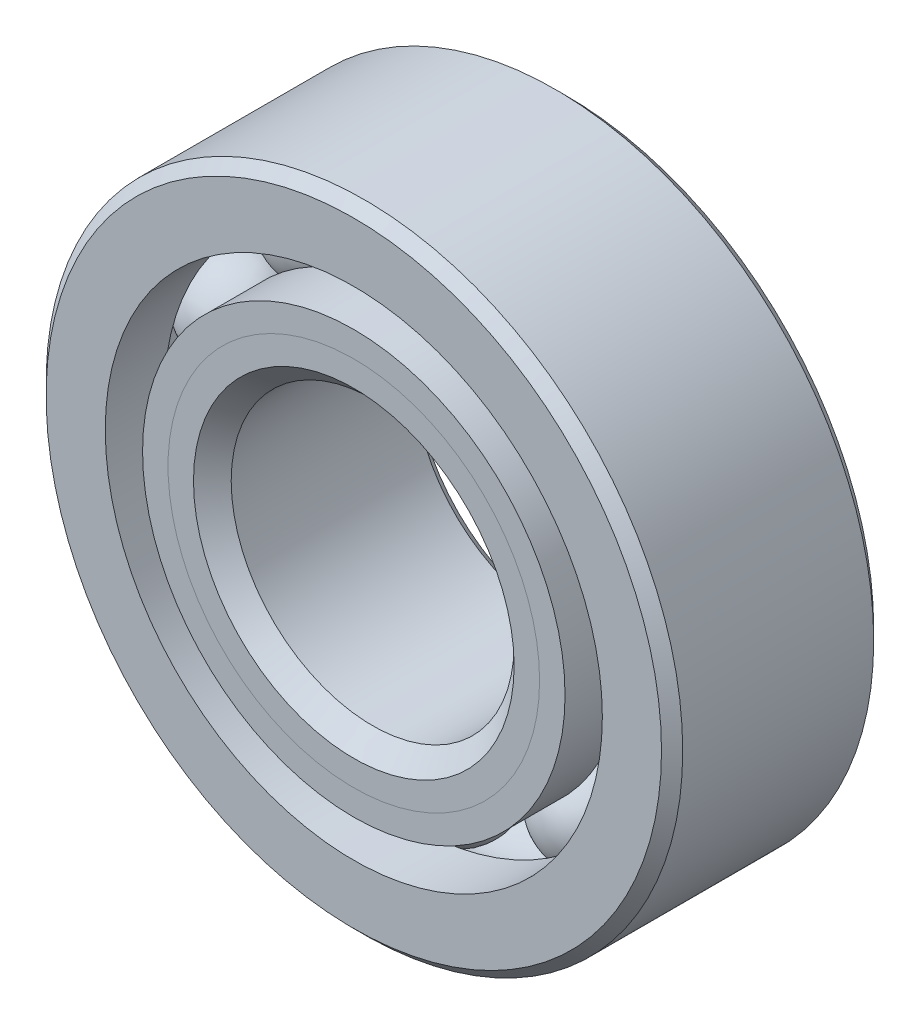
SolidWorks part; units mm, degrees
ref_plane "Front Plane" through (0, 0, 0) normal (0, 0, 1) x (1, 0, 0)
ref_plane "Top Plane" through (0, 0, 0) normal (0, 1, 0) x (1, 0, 0)
ref_plane "Right Plane" through (0, 0, 0) normal (1, 0, 0) x (0, 0, -1)
sketch "Sketch1" plane through (0, 0, 0) normal (1, 0, 0) x (0, 0, -1)
  line L0 (-4.7625, 0) -> (4.7625, 0) construction
  line L1 (0, 14.2875) -> (0, -14.2875) construction
  line L2 (4.2863, 14.2875) -> (-4.2863, 14.2875)
  line L3 (-4.2863, 14.2875) -> (-4.7625, 13.8113)
  line L4 (-4.7625, 13.8113) -> (-4.7625, 11.1561)
  line L5 (-4.7625, 11.1561) -> (-2.1167, 11.1561)
  line L6 (4.7625, 11.1561) -> (2.1167, 11.1561)
  line L7 (4.7625, 13.8113) -> (4.7625, 11.1561)
  line L8 (4.2863, 14.2875) -> (4.7625, 13.8113)
  line L9 (0, 14.2875) -> (0, 10.3187) construction
  line L10 (0, 10.3187) -> (0, 6.35) construction
  arc A0 (-2.1167, 11.1561) -> (2.1167, 11.1561) centre (0, 10.3187) cw
  point P14 (0, 6.35)
  dimension "Width" = 9.525
  dimension "OD" = 28.575
  dimension "D1" = 45
  dimension "D2" = 0.4763
  dimension "D3" = 4.2333
  dimension "D4" = 0.8374
revolve "Revolve1" add sketch "Sketch1" angle 360 about L0
sketch "Sketch2" plane through (0, 0, 0) normal (1, 0, 0) x (0, 0, -1)
  line L0 (-4.7625, 9.4814) -> (-2.1167, 9.4814)
  line L1 (-4.7625, 13.8113) -> (-4.7625, -13.8113) construction
  line L2 (-4.7625, 9.4814) -> (-4.7625, 8.3388)
  line L3 (-4.7625, 8.3388) -> (-3.6199, 7.1962)
  line L4 (-3.6199, 7.1962) -> (0, 7.1962)
  line L5 (0, 14.2875) -> (0, -14.2875) construction
  line L6 (0, 7.1962) -> (0, 8.0425)
  line L7 (0, 8.0425) -> (0, 6.35) construction
  line L8 (-4.7625, 9.4814) -> (-4.7625, 7.1962) construction
  line L9 (-4.7625, 7.1962) -> (-3.6199, 7.1962) construction
  arc A0 (-2.1167, 9.4814) -> (0, 8.0425) centre (0, 10.3187) ccw
  arc A1 (2.1167, 11.1561) -> (-2.1167, 11.1561) centre (0, 10.3187) ccw construction
  circle A2 centre (0, 10.3187) radius 2.2763 construction
  dimension "D1" = 45
revolve "Revolve2" add sketch "Sketch2" angle 360 about L0
sketch "Sketch3" plane through (0, 0, 0) normal (1, 0, 0) x (0, 0, -1)
  line L0 (-4.7625, 8.3388) -> (-3.6199, 7.1962)
  line L1 (-3.6199, 7.1962) -> (0, 7.1962)
  line L2 (0, 7.1962) -> (0, 8.0425)
  line L3 (-4.7625, 8.3388) -> (-4.7625, 7.1962)
  line L4 (-4.7625, 9.4814) -> (-4.7625, 7.1962) construction
  line L5 (-4.7625, 7.1962) -> (-3.9163, 6.35)
  line L6 (-3.9163, 6.35) -> (4.2863, 6.35)
  line L7 (4.2863, 14.2875) -> (4.2863, -14.2875) construction
  line L8 (4.2863, 6.35) -> (4.7625, 6.8262)
  line L9 (4.7625, -13.8113) -> (4.7625, 13.8113) construction
  line L10 (4.7625, 6.8262) -> (4.7625, 9.4814)
  line L11 (4.7625, 9.4814) -> (2.1167, 9.4814)
  line L13 (4.2863, 14.2875) -> (4.7625, 13.8113) construction
  circle A0 centre (0, 10.3187) radius 2.2763 construction
  arc A1 (2.1167, 9.4814) -> (0, 8.0425) centre (0, 10.3187) cw
revolve "Revolve3" add sketch "Sketch3" angle 360 about L0
sketch "Sketch4" plane through (0, 0, 0) normal (1, 0, 0) x (0, 0, -1)
  line L0 (-2.2763, 10.3187) -> (2.2763, 10.3187)
  circle A1 centre (0, 10.3187) radius 2.2763 construction
  arc A2 (-2.2763, 10.3187) -> (2.2763, 10.3187) centre (0, 10.3187) cw
  arc A3 (2.1167, 11.1561) -> (-2.1167, 11.1561) centre (0, 10.3187) ccw construction
revolve "Revolve4" add sketch "Sketch4" angle 360 about L0
ref_axis "Axis1" through (0, 0, -4.7625) along (0, 0, 1)
pattern_circular "CirPattern1" count 10 every 36 about axis through (0, 0, -4.7625) along (0, 0, 1) of bodies 104
equation "\"D2@Sketch1\" = \"Width@Sketch1\"*.05"
equation "\"D3@Sketch1\" = \"Width@Sketch1\"/2.25"
equation "\"D4@Sketch1\" = (((\"OD@Sketch1\"-\"Width@Sketch1\")/2)/3.25)/3.5"
equation "\"D2@CirPattern1\" = 360/\"Balls@CirPattern1\""
